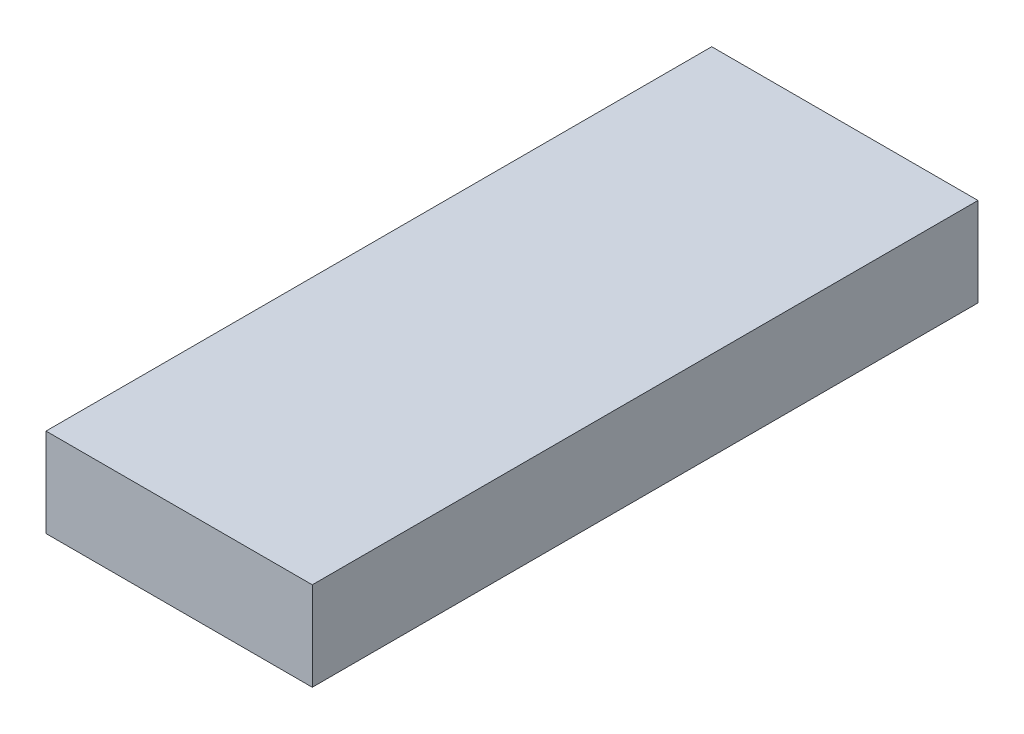
SolidWorks part; units mm, degrees
ref_plane "前视基准面" through (0, 0, 0) normal (0, 0, 1) x (1, 0, 0)
ref_plane "上视基准面" through (0, 0, 0) normal (0, 1, 0) x (1, 0, 0)
ref_plane "右视基准面" through (0, 0, 0) normal (1, 0, 0) x (0, 0, -1)
sketch "草图1" plane through (0, 0, 0) normal (0, 1, 0) x (1, 0, 0)
  line L1 (-1.3, 4.8) -> (1.3, 4.8)
  line L2 (-1.3, 4.8) -> (-1.3, -4.8)
  line L3 (-1.3, -4.8) -> (1.3, -4.8)
  line L4 (1.3, 4.8) -> (1.3, -4.8)
  line L5 (-1.3, 4.8) -> (1.3, -4.8) construction
  line L6 (-1.3, -4.8) -> (1.3, 4.8) construction
  line L7 (-3, 7.5) -> (3, 7.5)
  line L8 (-3, 7.5) -> (-3, -7.5)
  line L9 (-3, -7.5) -> (3, -7.5)
  line L10 (3, 7.5) -> (3, -7.5)
  line L11 (-3, 7.5) -> (3, -7.5) construction
  line L12 (-3, -7.5) -> (3, 7.5) construction
  point P0 (0, 0)
  point P6 (0, 0)
extrude "凸台-拉伸1" add sketch "草图1" along normal blind 1.3 contours L4 L1 L2 L3 region at (0, 0, 0)
extrude "凸台-拉伸2" add sketch "草图1<3>" along normal blind 2 from surface contours L10 L7 L8 L9 L1 L4 L3 L2 | L4 L1 L2 L3 region at (0, 0, 0) region at (0, 0, -7.3384) starting at face at (0, 1.3, 0)
sketch "草图1<3>" plane through (0, 0, 0) normal (0, 1, 0) x (1, 0, 0) same geometry as "草图1"
